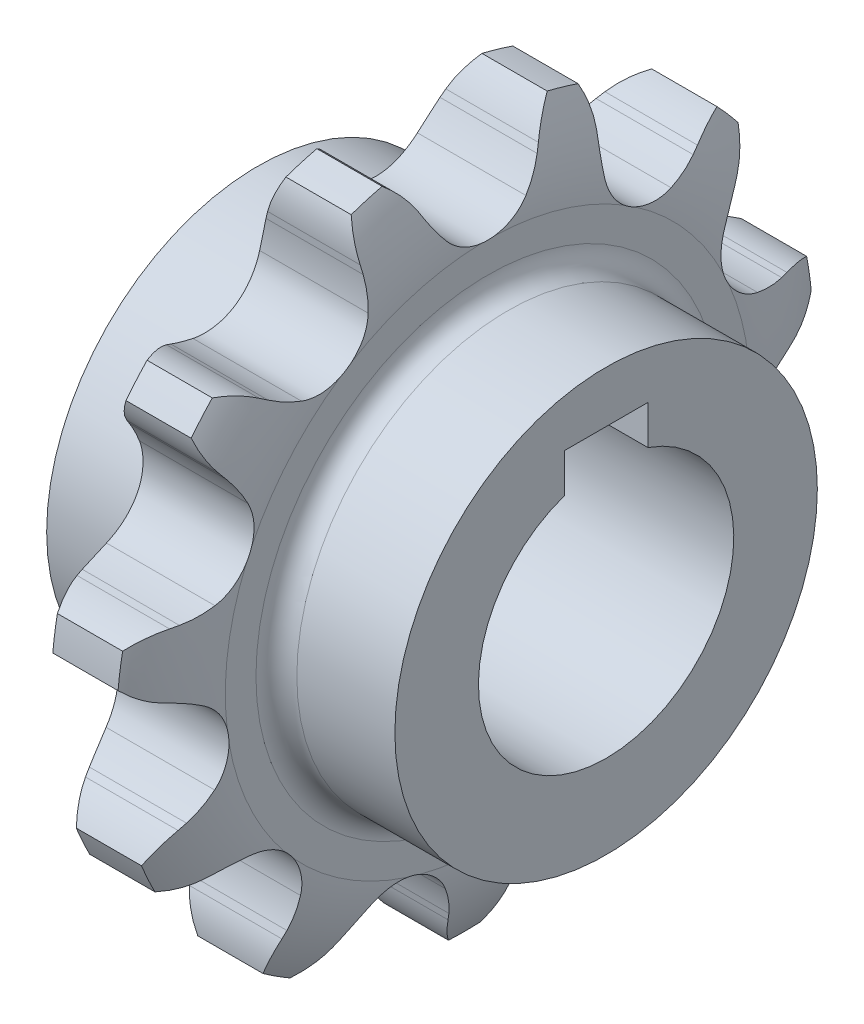
SolidWorks part; units mm, degrees
material "AISI 1020"
ref_plane "Front" through (0, 0, 0) normal (0, 0, 1) x (1, 0, 0)
ref_plane "Top" through (0, 0, 0) normal (0, 1, 0) x (1, 0, 0)
ref_plane "Right" through (0, 0, 0) normal (1, 0, 0) x (0, 0, -1)
sketch "Sketch1" plane through (0, 0, 0) normal (0, 0, 1) x (1, 0, 0)
  line L0 (-4, 0) -> (4, 0) construction
  line L1 (-17.4807, 0) -> (-17.4807, 45.5)
  line L2 (-17.4807, 45.5) -> (-16.3804, 45.5)
  line L3 (-11.9795, 49.9009) -> (-11.9795, 56.5023)
  line L4 (-7.0265, 75) -> (7.0265, 75)
  line L5 (11.9795, 56.5023) -> (11.9795, 49.9009)
  line L6 (16.3804, 45.5) -> (17.4807, 45.5)
  line L7 (17.4807, 45.5) -> (17.4807, 0)
  line L8 (17.4807, 0) -> (-17.4807, 0)
  line L9 (0, 0) -> (0, 75) construction
  line L10 (-10.2337, 67.6173) -> (10.2337, 67.6173) construction
  line L11 (-10.2337, -67.6173) -> (10.2337, -67.6173) construction
  line L13 (-11.9795, 56.5023) -> (3.7984, 56.5023) construction
  line L14 (-11.9795, -56.5023) -> (3.7984, -56.5023) construction
  arc A0 (-7.0265, 75) -> (-11.9795, 56.5023) centre (26.1194, 56.2128) ccw
  arc A1 (7.0265, 75) -> (11.9795, 56.5023) centre (-26.1194, 56.2128) cw
  arc A2 (11.9795, 49.9009) -> (16.3804, 45.5) centre (16.3804, 49.9009) ccw
  arc A3 (-16.3804, 45.5) -> (-11.9795, 49.9009) centre (-16.3804, 49.9009) ccw
  point P30 (11.9795, 45.5)
  point P33 (-11.9795, 45.5)
  point P34 (24, 26.331)
  point P36 (46.23, 26.331)
  point P37 (24, 21.8279)
  point P38 (60.2, 21.8279)
  point P39 (24, 17.1531)
  point P40 (49.22, 17.1531)
  point P41 (24, 13.3224)
  point P42 (69.44, 13.3224)
  point P43 (24, 30.8002)
  point P44 (35, 30.8002)
  point P45 (24, 35.1098)
  point P46 (62.1, 35.1098)
  dimension "D1" = 11.0023
  dimension "rx" = 38.1
  dimension "D3" = 4.4009
  dimension "d" = 135.2346
  dimension "p" = 38.1
  dimension "z" = 11
  dimension "da" = 150
  dimension "df" = 113.0046
  dimension "dr" = 22.23
  dimension "dg" = 91
  dimension "h" = 36.2
  dimension "bf1" = 23.959
  dimension "b1" = 25.22
  dimension "ba" = 4.953
  dimension "D2" = 5.5012
  dimension "pt" = 45.44
revolve "Revolve" add sketch "Sketch1" angle 360 about L0 other way angle 360
ref_axis "Axis1" through (-8.5448, 0, 0) along (1, 0, 0)
sketch "Sketch2" plane through (0, 0, 0) normal (1, 0, 0) x (0, 0, -1)
  line L0 (0, 0) -> (0, 75) construction
  line L1 (0, 0) -> (-21.1299, 71.962) construction
  line L2 (0, 0) -> (-40.5481, 63.094) construction
  line L3 (8.538, 60.3369) -> (17.7312, 52.4978) construction
  line L4 (12.1845, 65.7431) -> (-13.5322, 79.1564) construction
  line L5 (0, 0) -> (21.1299, 71.962) construction
  line L6 (12.1845, 65.7431) -> (12.9389, 67.1894)
  line L7 (-12.1845, 65.7431) -> (-12.9389, 67.1894)
  circle A0 centre (0, 0) radius 75 construction
  arc A1 (8.538, 60.3369) -> (-8.538, 60.3369) centre (0, 67.6173) cw
  arc A2 (8.538, 60.3369) -> (12.1845, 65.7431) centre (-13.5322, 79.1564) ccw
  arc A3 (17.7775, 72.8626) -> (12.9389, 67.1894) centre (27.7284, 59.4755) ccw
  arc A4 (-8.538, 60.3369) -> (-12.1845, 65.7431) centre (13.5322, 79.1564) cw
  arc A5 (-17.7775, 72.8626) -> (-12.9389, 67.1894) centre (-27.7284, 59.4755) cw
  arc A7 (17.7775, 72.8626) -> (-17.7775, 72.8626) centre (0, 0) ccw
  dimension "r1" = 11.2206
  dimension "r3" = 16.6804
  dimension "D1" = 32.727
  dimension "D2" = 16.364
  dimension "av2" = 49.545
  dimension "M" = 13.5322
  dimension "T" = 11.5391
  dimension "beta" = 12.909
  dimension "yv2" = 11.182
  dimension "bc" = 1.6312
extrude "ExtrudeCutOne" cut sketch "Sketch2" against normal mid plane 34.9613
pattern_circular "PatternOne" count 11 over 360 about axis through (-4, 0, 0) along (1, 0, 0) of "ExtrudeCutOne"
sketch "Cut-ExtrudeA" plane through (0, 0, 0) normal (1, 0, 0) x (0, 0, -1)
  circle A0 centre (0, 0) radius 30
sketch "SketchKey" plane through (0, 0, 0) normal (1, 0, 0) x (0, 0, -1)
  line L1 (-9, 15) -> (9, 15)
  line L2 (-9, 15) -> (-9, 34.4)
  line L3 (-9, 34.4) -> (9, 34.4)
  line L4 (9, 15) -> (9, 34.4)
extrude "Cut-ExtrudeB" cut sketch "SketchKey" against normal through all and the other way through all
sketch "草图3" plane through (17.4807, 0, 0) normal (1, 0, 0) x (0, 0, -1)
  circle A0 centre (0, 0) radius 27.5
  dimension "D1" = 55
extrude "切除-拉伸3" cut sketch "草图3" against normal up to next
sketch "草图4" plane through (-17.4807, 0, 0) normal (-1, 0, 0) x (0, 0, 1)
  line L0 (9, 34.4) -> (9, 25.9856) construction
  line L1 (9, 34.4) -> (9, 25.9856)
  line L2 (-9, 25.9856) -> (-9, 34.4) construction
  line L3 (-9, 25.9856) -> (-9, 34.4)
  line L4 (-9, 34.4) -> (9, 34.4) construction
  line L5 (-9, 34.4) -> (9, 34.4)
  arc A0 (-9, 25.9856) -> (9, 25.9856) centre (0, 0) ccw construction
  circle A1 centre (0, 0) radius 45.5
  circle A2 centre (0, 0) radius 45.5
  arc A3 (-9, 25.9856) -> (9, 25.9856) centre (0, 0) ccw
  dimension "D1" = 0
extrude "凸台-拉伸1" add sketch "草图4" along normal blind 20.02
sketch "草图5" plane through (17.4807, 0, 0) normal (1, 0, 0) x (0, 0, -1)
  line L0 (9, 25.9856) -> (9, 34.4) construction
  line L1 (9, 25.9856) -> (9, 34.4)
  line L2 (9, 34.4) -> (-9, 34.4) construction
  line L3 (9, 34.4) -> (-9, 34.4)
  line L4 (-9, 34.4) -> (-9, 25.9856) construction
  line L5 (-9, 34.4) -> (-9, 25.9856)
  arc A0 (-9, 25.9856) -> (9, 25.9856) centre (0, 0) ccw construction
  circle A1 centre (0, 0) radius 45.5
  circle A2 centre (0, 0) radius 45.5
  arc A3 (-9, 25.9856) -> (9, 25.9856) centre (0, 0) ccw
  dimension "D1" = 0
extrude "凸台-拉伸2" add sketch "草图5" along normal blind 20.02
